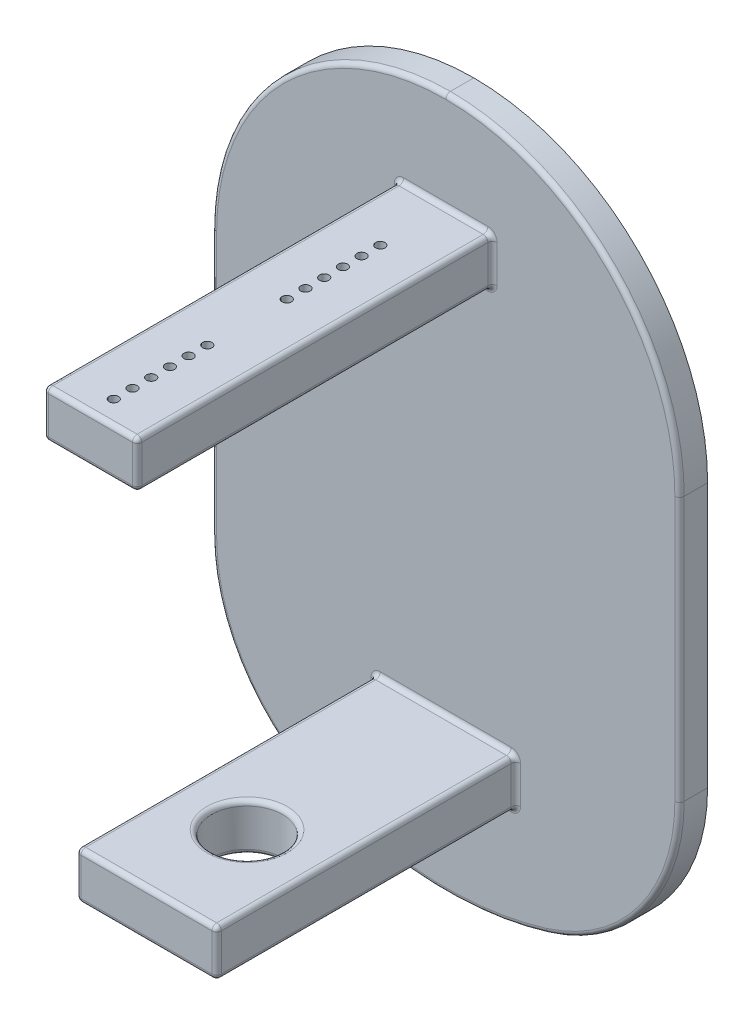
SolidWorks part; units mm, degrees
ref_plane "Front Plane" through (0, 0, 0) normal (0, 0, 1) x (1, 0, 0)
ref_plane "Top Plane" through (0, 0, 0) normal (0, 1, 0) x (1, 0, 0)
ref_plane "Right Plane" through (0, 0, 0) normal (1, 0, 0) x (0, 0, -1)
sketch "Sketch1" plane through (0, 0, 0) normal (0, 0, 1) x (1, 0, 0)
  circle A0 centre (0, 0) radius 37
  dimension "D1" = 74
extrude "Boss-Extrude1" add sketch "Sketch1" along normal blind 3
sketch "Sketch6" plane through (0, 0, 3) normal (0, 0, 1) x (1, 0, 0)
  line L0 (-25, 27.2764) -> (-25, -27.2764)
  line L1 (25, -27.2764) -> (25, 27.2764)
  arc A0 (25, -27.2764) -> (25, 27.2764) centre (0, 0) ccw
  circle A1 centre (0, 0) radius 37
  arc A2 (-25, 27.2764) -> (-25, -27.2764) centre (0, 0) ccw
  dimension "D2" = 25
  dimension "D3" = 50
  dimension "D1" = 0
extrude "Cut-Extrude3" cut sketch "Sketch6" against normal blind 10
fillet "Fillet2" radius 25 2 edges at (-25, 27.2764, 1.5) (25, 27.2764, 1.5)
fillet "Fillet3" radius 20 2 edges at (25, -27.2764, 1.5) (-25, -27.2764, 1.5)
sketch "Sketch2" plane through (0, 0, 3) normal (0, 0, 1) x (1, 0, 0)
  line L1 (-5, 26.5) -> (5, 26.5)
  line L2 (-5, 26.5) -> (-5, 21.5)
  line L3 (-5, 21.5) -> (5, 21.5)
  line L4 (5, 26.5) -> (5, 21.5)
  line L5 (-5, 26.5) -> (5, 21.5) construction
  line L6 (-5, 21.5) -> (5, 26.5) construction
  point P0 (0, 24)
  dimension "D1" = 5
  dimension "D2" = 26.5
  dimension "D3" = 10
extrude "Boss-Extrude2" add sketch "Sketch2" along normal blind 38
sketch "Sketch3" plane through (0, 26.5, 0) normal (0, 1, 0) x (1, 0, 0)
  line L0 (5, -3) -> (-5, -3) construction
  line L1 (5, -41) -> (-5, -41) construction
  circle A0 centre (0, -10) radius 0.5
  circle A1 centre (0, -12) radius 0.5
  circle A2 centre (0, -14) radius 0.5
  circle A3 centre (0, -16) radius 0.5
  circle A4 centre (0, -18) radius 0.5
  circle A5 centre (0, -20) radius 0.5
  circle A6 centre (0, -38.5) radius 0.5
  circle A7 centre (0, -36.5) radius 0.5
  circle A8 centre (0, -34.5) radius 0.5
  circle A9 centre (0, -32.5) radius 0.5
  circle A10 centre (0, -30.5) radius 0.5
  circle A11 centre (0, -28.5) radius 0.5
  point P20 (0, -41)
  dimension "D2" = 1
  dimension "D5" = 8.5
  dimension "D6" = 2
  dimension "D1" = 7
  dimension "D7" = 2
  dimension "D3" = 6
  dimension "D4" = 6
extrude "Cut-Extrude1" cut sketch "Sketch3" against normal blind 5
sketch "Sketch4" plane through (0, 0, 3) normal (0, 0, 1) x (1, 0, 0)
  line L1 (-7.5, -20.5) -> (7.5, -20.5)
  line L2 (-7.5, -20.5) -> (-7.5, -25.5)
  line L3 (-7.5, -25.5) -> (7.5, -25.5)
  line L4 (7.5, -20.5) -> (7.5, -25.5)
  line L5 (-7.5, -20.5) -> (7.5, -25.5) construction
  line L6 (-7.5, -25.5) -> (7.5, -20.5) construction
  line L7 (-5, 21.5) -> (5, 21.5) construction
  point P0 (0, -23)
  dimension "D1" = 42
  dimension "D2" = 15
  dimension "D3" = 5
extrude "Boss-Extrude3" add sketch "Sketch4" along normal blind 32
sketch "Sketch5" plane through (0, -20.5, 0) normal (0, 1, 0) x (1, 0, 0)
  line L0 (-7.5, -3) -> (7.5, -3) construction
  circle A0 centre (0, -24.25) radius 3.8
  dimension "D1" = 21.25
  dimension "D2" = 7.6
extrude "Cut-Extrude2" cut sketch "Sketch5" against normal blind 28
fillet "Fillet4" radius 0.5 33 edges at (-7.5, -25.5, 19) (0, -25.5, 35) (7.5, -25.5, 19) (0, -25.5, 28.05) (7.5, -20.5, 19) (0, -20.5, 35) (-7.5, -20.5, 19) (0, -20.5, 28.05) (5, 21.5, 22) (-5, 21.5, 22) (0, 21.5, 41) (5, 26.5, 22) (0, 26.5, 41) (-5, 26.5, 22) (-7.5, -23, 3) (0, -25.5, 3) (7.5, -23, 3) (0, -20.5, 3) (-5, 24, 3) (0, 21.5, 3) (5, 24, 3) (0, 26.5, 3) (-21.088, -28.1298, 3) (-25, -2.124, 3) (-17.6777, 29.6777, 3) (17.6777, 29.6777, 3) (25, -2.124, 3) (21.088, -28.1298, 3) (0, -37, 3) (7.5, -23, 35) (-7.5, -23, 35) (-5, 24, 41) (5, 24, 41)
